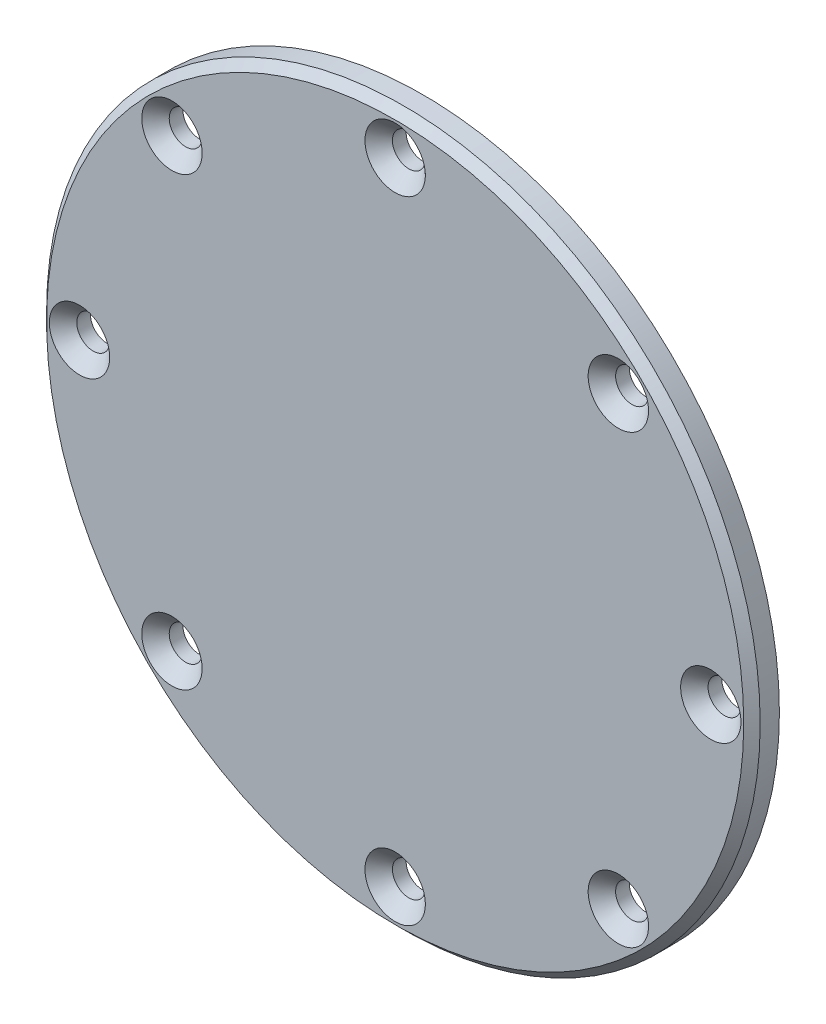
SolidWorks part; units mm, degrees
material "ABS"
ref_plane "Спереди" through (0, 0, 0) normal (0, 0, 1) x (1, 0, 0)
ref_plane "Сверху" through (0, 0, 0) normal (0, 1, 0) x (1, 0, 0)
ref_plane "Справа" through (0, 0, 0) normal (1, 0, 0) x (0, 0, -1)
sketch "Эскиз1" plane through (0, 0, 0) normal (0, 0, 1) x (1, 0, 0)
  circle A0 centre (0, 0) radius 26
  dimension "D1" = 52
extrude "Бобышка-Вытянуть1" add sketch "Эскиз1" along normal blind 2
chamfer "Фаска2" distance 0.6 angle 45 1 edges at (26, 0, 2)
hole_wizard "Зенковка для винта с полупотайной головкой M21" positions "Эскиз2" profile "Эскиз3" countersink size "M2" standard "DIN"
sketch "Эскиз2" plane through (0, 0, 2) normal (0, 0, 1) x (1, 0, 0)
  line L0 (-23, 0) -> (23, 0) construction
  circle A0 centre (0, 0) radius 23 construction
  point P0 (-23, 0)
  dimension "D1" = 46
sketch "Эскиз3" plane through (-23, 0, 2) normal (1, 0, 0) x (0, -1, 0)
  line L0 (0, 0) -> (0, 6.721)
  line L1 (0, 6.721) -> (1.2, 6)
  line L2 (1.2, 6) -> (1.2, 1)
  line L3 (1.2, 1) -> (2.2, 0)
  line L5 (2.2, 0) -> (0, 0)
  line L6 (-1.2, 1) -> (-2.2, 0) construction
  line L10 (0, 6.721) -> (-1.2, 6) construction
  line L11 (0, -6.35) -> (0, 107.95) construction
  dimension "Диаметр отверстия" = 2.4
  dimension "Глубина отверстия" = 6
  dimension "Диаметр передней зенковки" = 4.4
  dimension "Угол передней зенковки" = 90
  dimension "Угол заточки сверла" = 118
pattern_circular "Круговой массив1" count 8 over 360 about axis through (0, 0, 2) along (0, 0, 1) of "Зенковка для винта с полупотайной головкой M21"
